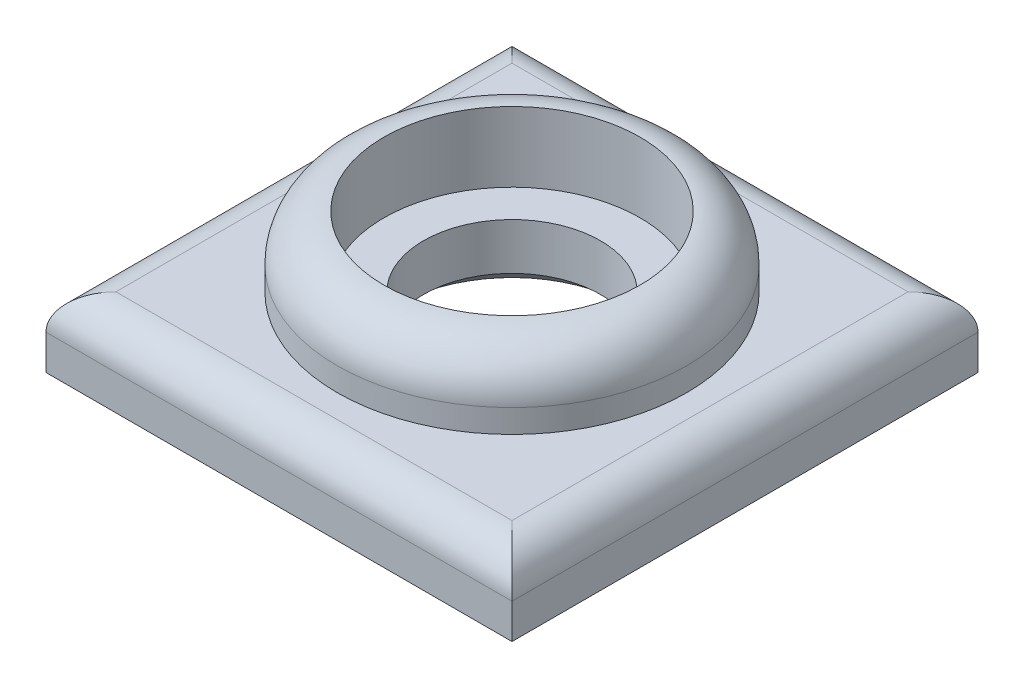
SolidWorks part; units mm, degrees
ref_plane "Спереди" through (0, 0, 0) normal (0, 0, 1) x (1, 0, 0)
ref_plane "Сверху" through (0, 0, 0) normal (0, 1, 0) x (1, 0, 0)
ref_plane "Справа" through (0, 0, 0) normal (1, 0, 0) x (0, 0, -1)
sketch "Sketch1" plane through (0, 0, 0) normal (0, 1, 0) x (1, 0, 0)
  line L1 (10, -10) -> (-10, -10)
  line L2 (10, -10) -> (10, 10)
  line L3 (10, 10) -> (-10, 10)
  line L4 (-10, -10) -> (-10, 10)
  line L5 (10, -10) -> (-10, 10) construction
  line L6 (10, 10) -> (-10, -10) construction
  circle A0 centre (0, 0) radius 3.8
  point P0 (0, 0)
  dimension "D2" = 7.6
  dimension "D1" = 20
extrude "Boss-Extrude1" add sketch "Sketch1" along normal blind 3
fillet "Fillet1" radius 1.5 4 edges at (0, 3, -10) (10, 3, 0) (0, 3, 10) (-10, 3, 0)
chamfer "Chamfer1" distance 1 angle 50 1 edges at (0, 0, 3.8) first distance on face at (0, 3, 3.8)
sketch "Sketch2" plane through (0, 3, 0) normal (0, 1, 0) x (1, 0, 0)
  circle A0 centre (0, 0) radius 5.5
  circle A1 centre (0, 0) radius 7.5
  dimension "D1" = 2
  dimension "D2" = 11
extrude "Boss-Extrude2" add sketch "Sketch2" along normal blind 3
fillet "Fillet2" radius 2 1 edges at (0, 6, 7.5)
